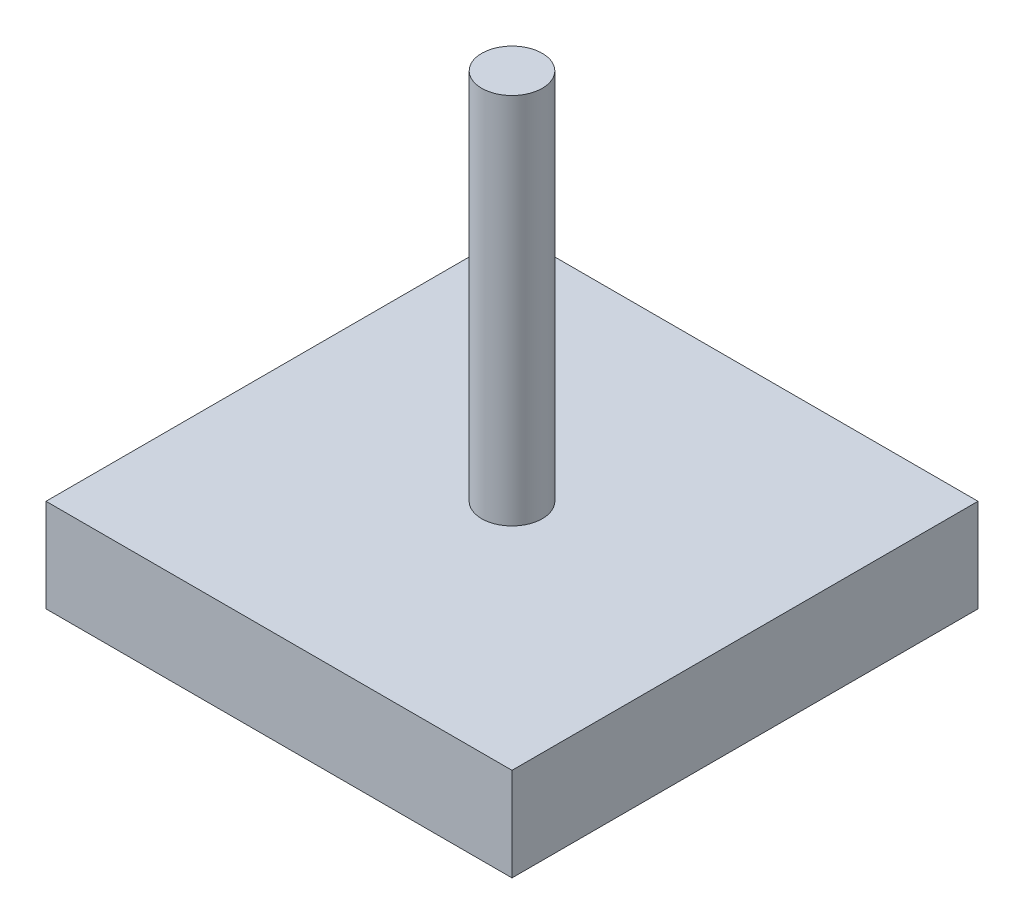
SolidWorks part; units mm, degrees
ref_plane "Front Plane" through (0, 0, 0) normal (0, 0, 1) x (1, 0, 0)
ref_plane "Top Plane" through (0, 0, 0) normal (0, 1, 0) x (1, 0, 0)
ref_plane "Right Plane" through (0, 0, 0) normal (1, 0, 0) x (0, 0, -1)
sketch "Sketch1" plane through (0, 0, 0) normal (0, 1, 0) x (1, 0, 0)
  line L1 (0, 0) -> (-50, 0)
  line L2 (0, 0) -> (0, 50)
  line L3 (0, 50) -> (-50, 50)
  line L4 (-50, 0) -> (-50, 50)
  circle A0 centre (-25, 25) radius 3.25
  dimension "D3" = 6.5
  dimension "D1" = 50
  dimension "D2" = 50
extrude "Boss-Extrude2" add sketch "Sketch1" along normal blind 50 contours A0
extrude "Boss-Extrude3" add sketch "Sketch1<5>" along normal blind 10
sketch "Sketch1<5>" plane through (0, 0, 0) normal (0, 1, 0) x (1, 0, 0) same geometry as "Sketch1"
